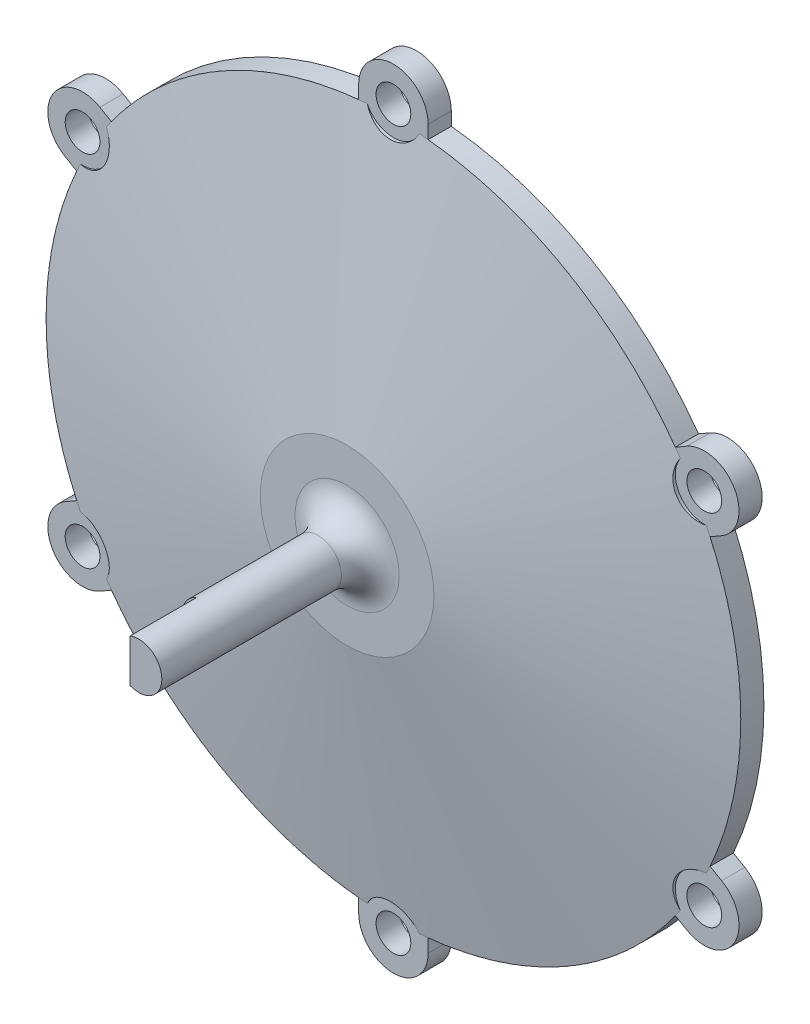
SolidWorks part; units mm, degrees
ref_plane "Front Plane" through (0, 0, 0) normal (0, 0, 1) x (1, 0, 0)
ref_plane "Top Plane" through (0, 0, 0) normal (0, 1, 0) x (1, 0, 0)
ref_plane "Right Plane" through (0, 0, 0) normal (1, 0, 0) x (0, 0, -1)
sketch "Sketch1" plane through (0, 0, 0) normal (0, 0, 1) x (1, 0, 0)
  line L0 (-6, 62) -> (-6, 59.6992)
  line L1 (6, 62) -> (6, 59.6992)
  line L2 (50.6936, 36.1962) -> (48.7011, 35.0458)
  line L3 (56.6936, 25.8038) -> (54.7011, 24.6535)
  line L4 (56.6936, -25.8038) -> (54.7011, -24.6535)
  line L5 (50.6936, -36.1962) -> (48.7011, -35.0458)
  line L6 (6, -62) -> (6, -59.6992)
  line L7 (-6, -62) -> (-6, -59.6992)
  line L8 (-50.6936, -36.1962) -> (-48.7011, -35.0458)
  line L9 (-56.6936, -25.8038) -> (-54.7011, -24.6535)
  line L10 (-56.6936, 25.8038) -> (-54.7011, 24.6535)
  line L11 (-50.6936, 36.1962) -> (-48.7011, 35.0458)
  line L12 (0, 0) -> (6, 59.6992) construction
  circle A0 centre (0, 0) radius 57
  circle A1 centre (0, 0) radius 60
  arc A2 (6, 62) -> (-6, 62) centre (0, 62) ccw
  arc A3 (56.6936, 25.8038) -> (50.6936, 36.1962) centre (53.6936, 31) ccw
  arc A4 (50.6936, -36.1962) -> (56.6936, -25.8038) centre (53.6936, -31) ccw
  arc A5 (-6, -62) -> (6, -62) centre (0, -62) ccw
  arc A6 (-56.6936, -25.8038) -> (-50.6936, -36.1962) centre (-53.6936, -31) ccw
  arc A7 (-50.6936, 36.1962) -> (-56.6936, 25.8038) centre (-53.6936, 31) ccw
  dimension "D1" = 120
  dimension "D2" = 3
  dimension "D3" = 6
  dimension "D4" = 62
  dimension "D5" = 6
extrude "Boss-Extrude1" add sketch "Sketch1" along normal blind 4 contours L11 A7 L10 A1 | L1 A2 L0 A1 | L3 A3 L2 A1 | L5 A4 L4 A1 | L7 A5 L6 A1 | L9 A6 L8 A1 | A0 A1 region at (0, 63.4372, 0) region at (0, 58.3029, 0) region at (-54.9382, 31.7186, 0) region at (54.9382, 31.7186, 0) region at (-54.9382, -31.7186, 0) region at (54.9382, -31.7186, 0) region at (0, -63.4372, 0)
sketch "Sketch3" plane through (0, 0, 0) normal (0, 1, 0) x (1, 0, 0)
  line L0 (0, -4) -> (60, -4)
  line L1 (-6, -4) -> (6, -4) construction
  line L2 (60, -4) -> (15, -12)
  line L3 (15, -12) -> (0, -12)
  line L4 (0, -12) -> (0, -4)
  line L5 (48.7011, 0) -> (6, 0) construction
  line L6 (48.7011, 0) -> (6, 0) construction
  line L7 (0, -4) -> (60, -4)
  line L8 (0, -4) -> (0, -0.5)
  line L9 (0, -0.5) -> (57, -0.5)
  line L13 (57, -0.5) -> (57, -4)
  line L15 (-57, -4) -> (57, -4) construction
  dimension "D1" = 12
  dimension "D2" = 15
  dimension "D3" = 0.5
  dimension "D4" = 3
revolve "Revolve1" add sketch "Sketch3" angle 360 about L4 region at (28.5, 0, 2.25) region at (21, 0, 7.2)
sketch "Sketch4" plane through (0, 0, 0.5) normal (0, 0, 1) x (1, 0, 0)
  circle A0 centre (0, 0) radius 14
  dimension "D1" = 28
extrude "Cut-Extrude1" cut sketch "Sketch4" along normal blind 7 contours A0
sketch "Sketch9" plane through (0, 0, 7.5) normal (0, 0, -1) x (-1, 0, 0)
  circle A0 centre (0, 0) radius 11.5
  dimension "D1" = 23
extrude "Cut-Extrude4" cut sketch "Sketch9" against normal blind 0.5
sketch "Sketch10" plane through (0, 0, 12) normal (0, 0, 1) x (1, 0, 0)
  circle A0 centre (0, 0) radius 4
  dimension "D1" = 8
extrude "Boss-Extrude2" add sketch "Sketch10" along normal blind 36
fillet "Fillet1" radius 5 1 edges at (4, 0, 12)
sketch "Sketch7" plane through (0, 0, 4) normal (0, 0, 1) x (1, 0, 0)
  circle A0 centre (0, 62) radius 3
  arc A1 (6, 62) -> (-6, 62) centre (0, 62) ccw construction
  dimension "D1" = 6
extrude "Cut-Extrude2" cut sketch "Sketch7" against normal through all
sketch "Sketch8" plane through (0, 0, 4) normal (0, 0, 1) x (1, 0, 0)
  circle A0 centre (0, 62) radius 5
  dimension "D1" = 10
extrude "Cut-Extrude3" cut sketch "Sketch8" along normal through all
pattern_circular "CirPattern6" count 6 over 360 about axis through (0, 0, 4) along (0, 0, 1) of "Cut-Extrude2", "Cut-Extrude3"
sketch "Sketch11" plane through (0, 0, 48) normal (0, 0, 1) x (1, 0, 0)
  line L1 (-1.5, 3.7081) -> (-4, 3.7081)
  line L2 (-1.5, 3.7081) -> (-1.5, -3.7081)
  line L3 (-1.5, -3.7081) -> (-4, -3.7081)
  line L4 (-4, 3.7081) -> (-4, -3.7081)
  circle A0 centre (0, 0) radius 4 construction
  dimension "D1" = 2.5
extrude "Cut-Extrude5" cut sketch "Sketch11" against normal blind 11.5
